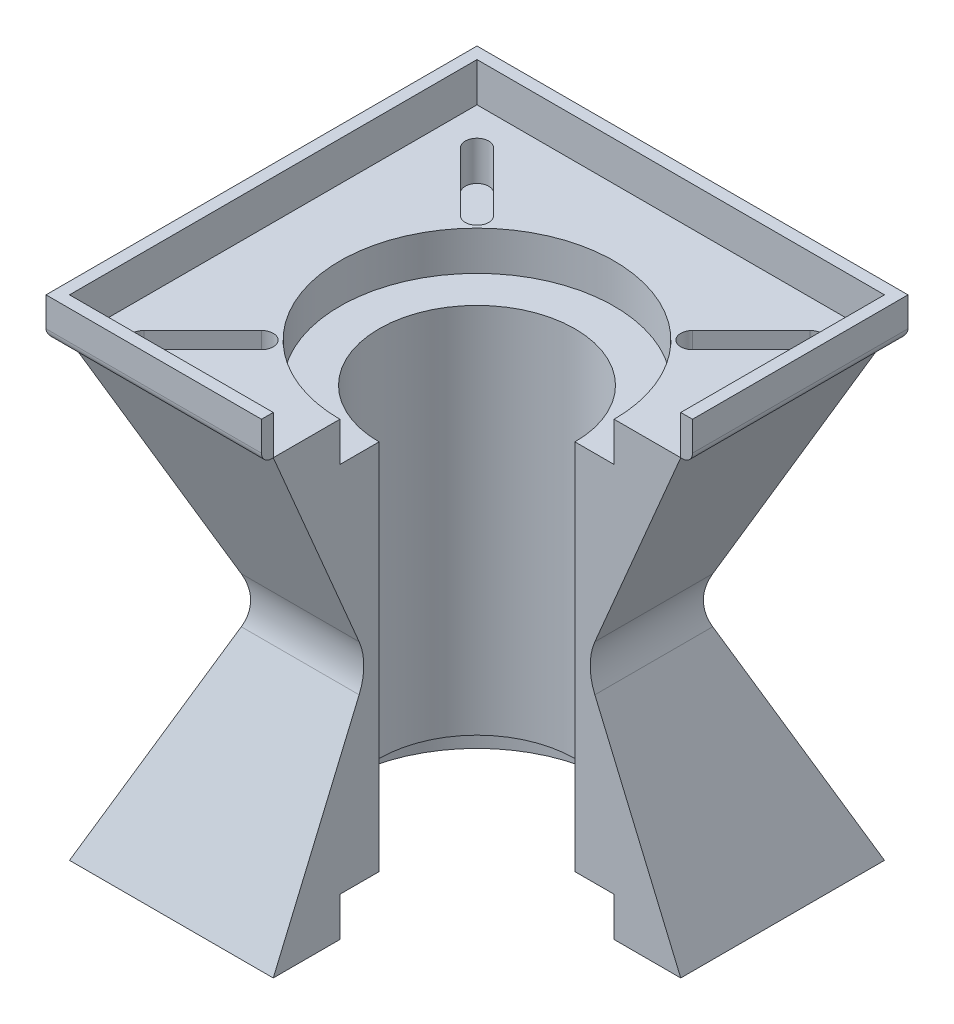
SolidWorks part; units mm, degrees
material "Cast Stainless Steel"
ref_plane "Front Plane" through (0, 0, 0) normal (0, 0, 1) x (1, 0, 0)
ref_plane "Top Plane" through (0, 0, 0) normal (0, 1, 0) x (1, 0, 0)
ref_plane "Right Plane" through (0, 0, 0) normal (1, 0, 0) x (0, 0, -1)
sketch "Sketch2" plane through (0, 0, 0) normal (0, 1, 0) x (1, 0, 0)
  line L1 (0, 0) -> (104, 0)
  line L2 (0, 0) -> (0, 104)
  line L3 (0, 104) -> (104, 104)
  line L4 (104, 0) -> (104, 104)
  dimension "D1" = 104
  dimension "D2" = 104
extrude "Boss-Extrude1" add sketch "Sketch2" along normal blind 57.5 draft 23
mirror "Mirror2" about plane through (0, 57.5, 0) normal (0, -1, 0) of bodies 101
sketch "Sketch4" plane through (0, 115, 0) normal (0, 1, 0) x (1, 0, 0)
  line L0 (0, 0) -> (104, 0) construction
  line L1 (104, 0) -> (104, 104) construction
  line L2 (0, 104) -> (0, 0) construction
  line L3 (104, 104) -> (0, 104) construction
  line L4 (0, 0) -> (104, 0)
  line L5 (104, 0) -> (104, 104)
  line L6 (0, 104) -> (0, 0)
  line L7 (104, 104) -> (0, 104)
  circle A0 centre (52, 52) radius 25
  dimension "D1" = 50
extrude "Cut-Extrude1" cut sketch "Sketch4" against normal through all both and the other way through all contours A0
fillet "Fillet1" radius 15 4 edges at (52, 57.5, -79.5927) (79.5927, 57.5, -52) (52, 57.5, -24.4073) (24.4073, 57.5, -52)
sketch "Sketch5" plane through (0, 115, 0) normal (0, 1, 0) x (1, 0, 0)
  circle A0 centre (52, 52) radius 35
  dimension "D1" = 70
extrude "Cut-Extrude2" cut sketch "Sketch5" against normal blind 10
sketch "Sketch6" plane through (0, 0, 0) normal (0, -1, 0) x (1, 0, 0)
  circle A0 centre (52, -52) radius 35
  dimension "D1" = 70
extrude "Cut-Extrude3" cut sketch "Sketch6" against normal blind 10
sketch "Sketch7" plane through (0, 115, 0) normal (0, 1, 0) x (1, 0, 0)
  line L1 (52, 52) -> (104, 52)
  line L2 (52, 52) -> (52, 0)
  line L3 (52, 0) -> (104, 0)
  line L4 (104, 52) -> (104, 0)
extrude "Cut-Extrude4" cut sketch "Sketch7" against normal through all
sketch "Sketch8" plane through (0, 115, 0) normal (0, 1, 0) x (1, 0, 0)
  line L0 (104, 52) -> (104, 104) construction
  line L3 (0, 0) -> (52, 0) construction
  line L4 (0, 104) -> (0, 0) construction
  line L5 (104, 104) -> (0, 104) construction
  line L6 (104, 52) -> (104, 104)
  line L7 (107, 52) -> (107, 107)
  line L8 (107, 107) -> (-3, 107)
  line L9 (0, 0) -> (52, 0)
  line L10 (0, 104) -> (0, 0)
  line L11 (104, 104) -> (0, 104)
  line L12 (-3, 107) -> (-3, -3)
  line L13 (-3, -3) -> (52, -3)
  line L14 (52, -3) -> (52, 0)
  line L15 (104, 52) -> (107, 52)
  dimension "D1" = 3
extrude "Boss-Extrude3" add sketch "Sketch8" along normal blind 10 separate body
fillet "Fillet12" radius 2.5 4 edges at (24.5, 115, 3) (-3, 115, -52) (52, 115, -107) (107, 115, -79.5)
sketch "Sketch10" plane through (0, 115, 0) normal (0, 1, 0) x (1, 0, 0)
  line L0 (107, 107) -> (-3, -3) construction
  line L1 (-3, 107) -> (52, 52) construction
  line L2 (-3, 52) -> (52, 52) construction
  line L3 (-3, 107) -> (-3, -3) construction
  line L4 (52, 52) -> (52, 107) construction
  line L5 (107, 107) -> (-3, 107) construction
  line L6 (9.5, 94.5) -> (24.5, 79.5) construction
  line L7 (11.6213, 96.6213) -> (26.6213, 81.6213)
  line L8 (7.3787, 92.3787) -> (22.3787, 77.3787)
  line L9 (94.5, 94.5) -> (79.5, 79.5) construction
  line L10 (92.3787, 96.6213) -> (77.3787, 81.6213)
  line L11 (96.6213, 92.3787) -> (81.6213, 77.3787)
  line L12 (9.5, 9.5) -> (24.5, 24.5) construction
  line L13 (11.6213, 7.3787) -> (26.6213, 22.3787)
  line L14 (7.3787, 11.6213) -> (22.3787, 26.6213)
  arc A0 (11.6213, 96.6213) -> (7.3787, 92.3787) centre (9.5, 94.5) ccw
  arc A1 (22.3787, 77.3787) -> (26.6213, 81.6213) centre (24.5, 79.5) ccw
  arc A2 (92.3787, 96.6213) -> (96.6213, 92.3787) centre (94.5, 94.5) cw
  arc A3 (81.6213, 77.3787) -> (77.3787, 81.6213) centre (79.5, 79.5) cw
  arc A4 (11.6213, 7.3787) -> (7.3787, 11.6213) centre (9.5, 9.5) cw
  arc A5 (22.3787, 26.6213) -> (26.6213, 22.3787) centre (24.5, 24.5) cw
  point P15 (17, 87)
  point P22 (87, 87)
  point P29 (17, 17)
  dimension "D1" = 3
  dimension "D2" = 15
extrude "Cut-Extrude5" cut sketch "Sketch10" against normal blind 10
equation "\"A\"= 115mm"
equation "\"B\"= 104mm"
equation "\"C\"= 23mm"
equation "\"D1@Sketch2\"=\"B\""
equation "\"D2@Sketch2\"=\"B\""
